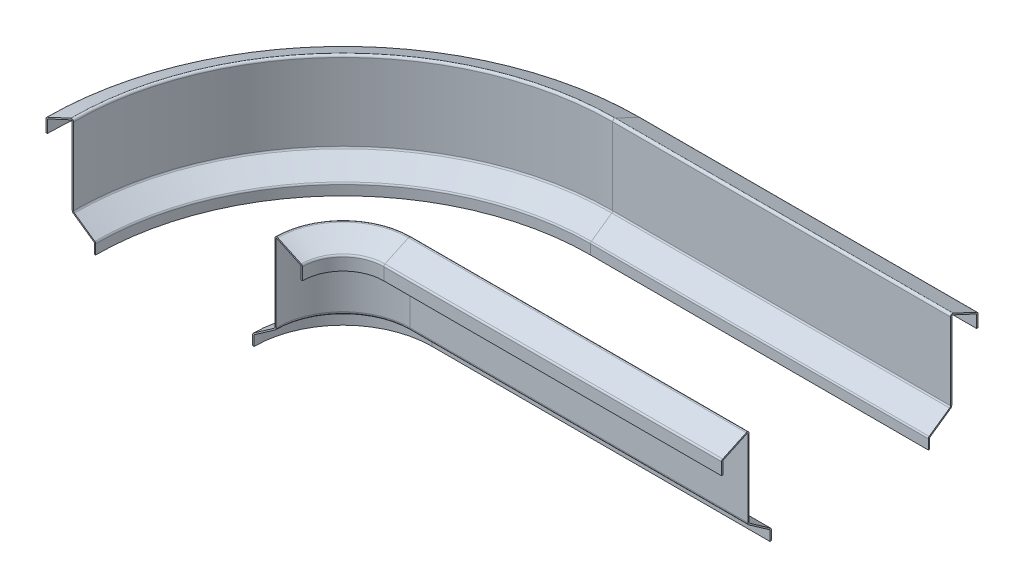
SolidWorks part; units mm, degrees
material "AISI 1015 Steel, Cold Drawn (SS)"
ref_plane "Front Plane" through (0, 0, 0) normal (0, 0, 1) x (1, 0, 0)
ref_plane "Top Plane" through (0, 0, 0) normal (0, 1, 0) x (1, 0, 0)
ref_plane "Right Plane" through (0, 0, 0) normal (1, 0, 0) x (0, 0, -1)
ref_plane "Plane1" through (0, 0, 25) normal (0, 0, 1) x (1, 0, 0)
ref_plane "Plane2" through (0, 55, 0) normal (0, 1, 0) x (1, 0, 0)
sketch "Sketch6" plane through (0, 0, 25) normal (0, 0, 1) x (1, 0, 0)
  line L14 (-118.2339, -26.0665) -> (-118.2339, -40.5048)
  line L15 (-118.2339, -40.5048) -> (-116.2339, -40.5048)
  line L16 (-116.2339, -40.5048) -> (-116.2339, -26.0665)
  line L17 (-117.5132, -23.609) -> (-147.7207, -2.4575)
  line L18 (-149, 0) -> (-149, 113.7292)
  line L19 (-153.2679, 116.4482) -> (-188.0517, 100.2282)
  line L20 (-189.7839, 97.5093) -> (-189.7839, 79.4205)
  line L21 (-189.7839, 79.4205) -> (-187.7839, 79.4205)
  line L22 (-187.7839, 79.4205) -> (-187.7839, 97.5093)
  line L23 (-187.2065, 98.4156) -> (-152.4226, 114.6355)
  line L24 (-151, 113.7292) -> (-151, 0)
  line L25 (-148.8679, -4.0958) -> (-118.6603, -25.2473)
  line L26 (0, -55) -> (0, 55) construction
  line L27 (148.8679, -4.0958) -> (118.6603, -25.2473)
  line L28 (151, 113.7292) -> (151, 0)
  line L29 (187.2065, 98.4156) -> (152.4226, 114.6355)
  line L30 (187.7839, 79.4205) -> (187.7839, 97.5093)
  line L31 (189.7839, 79.4205) -> (187.7839, 79.4205)
  line L32 (189.7839, 97.5093) -> (189.7839, 79.4205)
  line L33 (153.2679, 116.4482) -> (188.0517, 100.2282)
  line L34 (149, 0) -> (149, 113.7292)
  line L35 (117.5132, -23.609) -> (147.7207, -2.4575)
  line L36 (116.2339, -40.5048) -> (116.2339, -26.0665)
  line L37 (118.2339, -40.5048) -> (116.2339, -40.5048)
  line L38 (118.2339, -26.0665) -> (118.2339, -40.5048)
  line L40 (-149, 0) -> (149, 0) construction
  arc A8 (-116.2339, -26.0665) -> (-117.5132, -23.609) centre (-119.2339, -26.0665) ccw
  arc A9 (-149, 0) -> (-147.7207, -2.4575) centre (-146, 0) ccw
  arc A10 (-149, 113.7292) -> (-153.2679, 116.4482) centre (-152, 113.7292) ccw
  arc A11 (-188.0517, 100.2282) -> (-189.7839, 97.5093) centre (-186.7839, 97.5093) ccw
  arc A12 (-187.2065, 98.4156) -> (-187.7839, 97.5093) centre (-186.7839, 97.5093) ccw
  arc A13 (-151, 113.7292) -> (-152.4226, 114.6355) centre (-152, 113.7292) ccw
  arc A14 (-151, 0) -> (-148.8679, -4.0958) centre (-146, 0) ccw
  arc A15 (-118.2339, -26.0665) -> (-118.6603, -25.2473) centre (-119.2339, -26.0665) ccw
  arc A16 (118.2339, -26.0665) -> (118.6603, -25.2473) centre (119.2339, -26.0665) cw
  arc A17 (151, 0) -> (148.8679, -4.0958) centre (146, 0) cw
  arc A18 (151, 113.7292) -> (152.4226, 114.6355) centre (152, 113.7292) cw
  arc A19 (187.2065, 98.4156) -> (187.7839, 97.5093) centre (186.7839, 97.5093) cw
  arc A20 (188.0517, 100.2282) -> (189.7839, 97.5093) centre (186.7839, 97.5093) cw
  arc A21 (149, 113.7292) -> (153.2679, 116.4482) centre (152, 113.7292) cw
  arc A22 (149, 0) -> (147.7207, -2.4575) centre (146, 0) cw
  arc A23 (116.2339, -26.0665) -> (117.5132, -23.609) centre (119.2339, -26.0665) cw
  point P28 (0, 0)
  dimension "D2" = 3
  dimension "D3" = 1
  dimension "D4" = 116.2339
  dimension "D5" = 117.5132
  dimension "D6" = 152.4226
  dimension "D7" = 186.7839
  dimension "D8" = 79.4205
  dimension "D9" = 97.5093
  dimension "D10" = 40.5048
  dimension "D11" = 146
sketch "Sketch8" plane through (0, 55, 0) normal (0, 1, 0) x (1, 0, 0)
  line L0 (-149, -25) -> (149, -25) construction
  line L1 (250, 225) -> (750, 225)
  line L2 (-149.218, 0) -> (225, 0) construction
  line L3 (225, 0) -> (225, 374.218) construction
  line L4 (-142.0275, 73.0063) -> (225, 0) construction
  line L5 (-120.7323, 143.207) -> (225, 0) construction
  line L6 (-86.1509, 207.9044) -> (225, 0) construction
  line L7 (-39.6121, 264.6121) -> (225, 0) construction
  line L8 (17.0956, 311.1509) -> (225, 0) construction
  line L9 (81.793, 345.7323) -> (225, 0) construction
  line L10 (151.9937, 367.0275) -> (225, 0) construction
  line L13 (225, 0) -> (-149.218, 0) construction
  arc A0 (0, -25) -> (250, 225) centre (250, -25) cw
  arc A1 (-150, -25) -> (250, 375) centre (250, -25) cw construction
  arc A2 (150, -25) -> (250, 75) centre (250, -25) cw construction
  arc A3 (-149.218, 0) -> (225, 374.218) centre (225, 0) cw
  dimension "D1" = 250
  dimension "D3" = 400
  dimension "D7" = 100
  dimension "D2" = 500
  dimension "D4" = 25
  dimension "D5" = 25
  dimension "D8" = 11.25
  dimension "D6" = 8
sweep "Sweep1" add profiles "Sketch6" path "Sketch8"
ref_plane "Plane3" through (-149.218, 55, 0) normal (1, 0, 0) x (0, 0, -1)
ref_plane "Plane4" through (-142.0275, 55, -73.0063) normal (0.9808, 0, 0.1951) x (0.1951, 0, -0.9808)
ref_plane "Plane5" through (-120.7323, 55, -143.207) normal (0.9239, 0, 0.3827) x (0.3827, 0, -0.9239)
ref_plane "Plane6" through (-86.1509, 55, -207.9044) normal (0.8315, 0, 0.5556) x (0.5556, 0, -0.8315)
ref_plane "Plane7" through (-39.6121, 55, -264.6121) normal (0.7071, 0, 0.7071) x (0.7071, 0, -0.7071)
ref_plane "Plane8" through (17.0956, 55, -311.1509) normal (0.5556, 0, 0.8315) x (0.8315, 0, -0.5556)
ref_plane "Plane9" through (81.793, 55, -345.7323) normal (0.3827, 0, 0.9239) x (0.9239, 0, -0.3827)
ref_plane "Plane10" through (151.9937, 55, -367.0275) normal (0.1951, 0, 0.9808) x (0.9808, 0, -0.1951)
ref_plane "Plane11" through (225, 55, -374.218) normal (0, 0, -1) x (-1, 0, 0)
